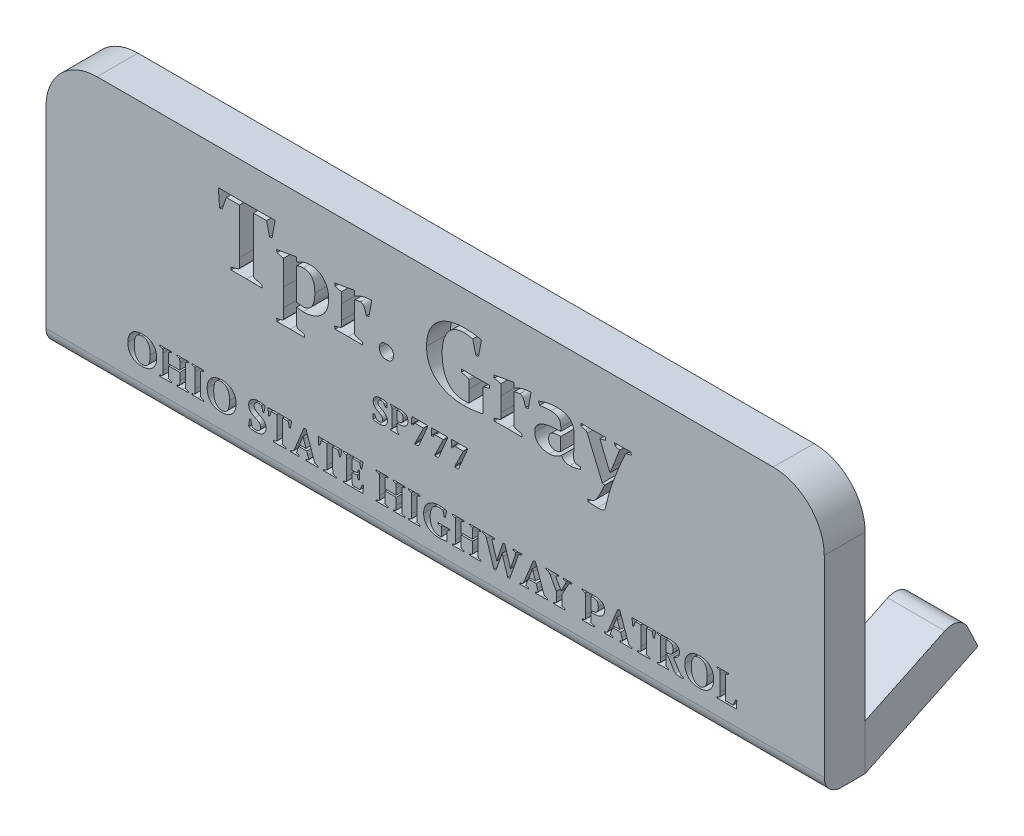
SolidWorks part; units mm, degrees
ref_plane "Front Plane" through (0, 0, 0) normal (0, 0, 1) x (1, 0, 0)
ref_plane "Top Plane" through (0, 0, 0) normal (0, 1, 0) x (1, 0, 0)
ref_plane "Right Plane" through (0, 0, 0) normal (1, 0, 0) x (0, 0, -1)
sketch "Sketch1" plane through (0, 0, 0) normal (0, 0, 1) x (1, 0, 0)
  line L1 (-108.803, -40.1851) -> (119.797, -40.1851)
  line L2 (-108.803, -40.1851) -> (-108.803, 21.3149)
  line L3 (-93.803, 36.3149) -> (104.797, 36.3149)
  line L4 (119.797, -40.1851) -> (119.797, 21.3149)
  arc A0 (104.797, 36.3149) -> (119.797, 21.3149) centre (104.797, 21.3149) cw
  arc A1 (-108.803, 21.3149) -> (-93.803, 36.3149) centre (-93.803, 21.3149) cw
  point P6 (119.797, 36.3149)
  dimension "D3" = 15
  dimension "D1" = 228.6
  dimension "D2" = 76.5
extrude "Boss-Extrude1" add sketch "Sketch1" along normal blind 12
sketch "Sketch2" plane through (119.797, 0, 0) normal (1, 0, 0) x (0, 0, -1)
  line L0 (0, -40.1851) -> (33.1567, -24.3437)
  line L1 (33.1567, -24.3437) -> (27.9311, -13.4062)
  line L2 (27.9311, -13.4062) -> (0, -26.7509)
  line L3 (0, -40.1851) -> (0, 21.3149) construction
  line L4 (0, -26.7509) -> (0, -40.1851)
extrude "Boss-Extrude2" add sketch "Sketch2" along normal blind 0.001 and the other way blind 228.6
sketch "Sketch3" plane through (0, -32.7169, -15.6312) normal (0, -0.9023, -0.4311) x (1, 0, 0)
  line L0 (-108.803, 17.3237) -> (119.797, 17.3237) construction
  line L1 (-92.003, 17.3237) -> (102.997, 17.3237)
  line L2 (-92.003, 17.3237) -> (-92.003, -19.423)
  line L3 (-92.003, -19.423) -> (102.997, -19.423)
  line L4 (102.997, 17.3237) -> (102.997, -19.423)
  line L5 (-108.803, -19.423) -> (119.798, -19.423) construction
  line L6 (-108.803, 17.3237) -> (-108.803, -19.423) construction
  line L7 (119.797, 17.3237) -> (119.798, -19.423) construction
  dimension "D1" = 195
  dimension "D2" = 16.8
  dimension "D3" = 16.8
extrude "Cut-Extrude1" cut sketch "Sketch3" against normal blind 13
fillet "Fillet2" radius 5 1 edges at (5.497, -40.1851, 12)
fillet "Fillet3" radius 5 1 edges at (5.497, -28.4551, 5.6043)
sketch "Sketch4" plane through (0, 0, 12) normal (0, 0, 1) x (1, 0, 0)
  text T0 "Tpr. Gray" font "Constantia" height in points 72
extrude "Cut-Extrude2" cut sketch "Sketch4" against normal blind 7
sketch "Sketch5" plane through (0, 0, 12) normal (0, 0, 1) x (1, 0, 0)
  text T0 "OHIO STATE HIGHWAY PATROL " font "Constantia" height in points 30
extrude "Cut-Extrude3" cut sketch "Sketch5" against normal blind 7
fillet "Fillet4" radius 5 2 edges at (-100.403, -13.4062, -27.9311) (111.3975, -13.4062, -27.9311)
sketch "Sketch6" plane through (0, 0, 12) normal (0, 0, 1) x (1, 0, 0)
  text T0 "SP777" font "Cambria" height in points 24
extrude "Cut-Extrude4" cut sketch "Sketch6" against normal blind 7
sketch "Sketch8" plane through (0, -32.7169, -15.6312) normal (0, -0.9023, -0.4311) x (1, 0, 0)
  text T0 "NS" font "Dutch801 Rm BT" height in points 26
extrude "Cut-Extrude5" cut sketch "Sketch8" against normal blind 5
